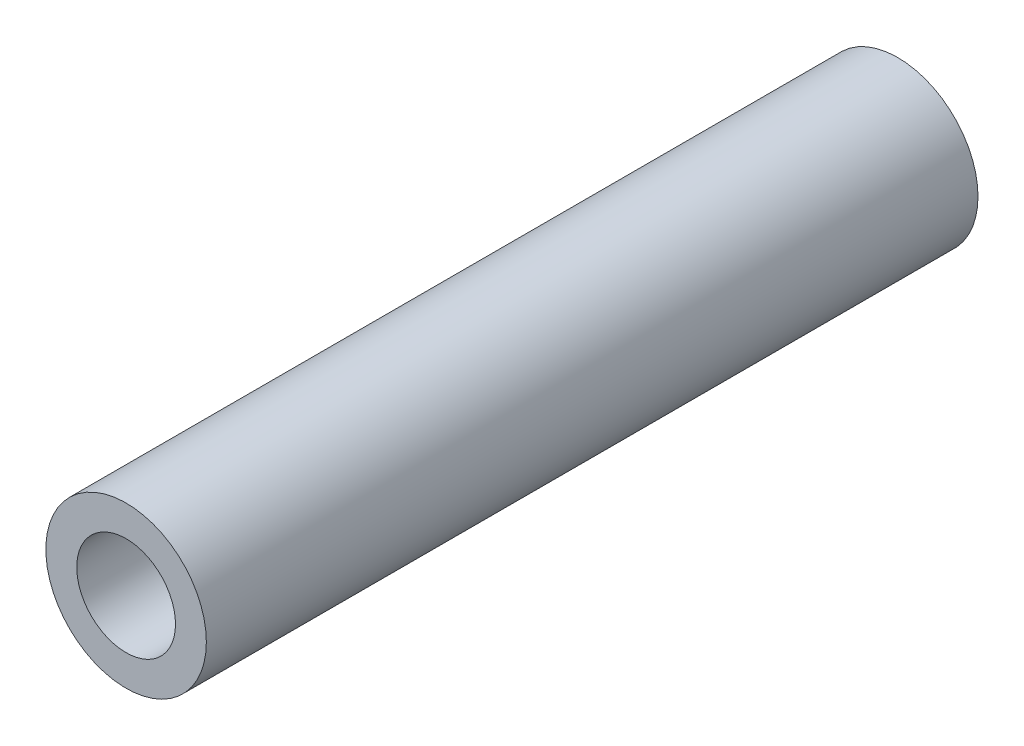
SolidWorks part; units mm, degrees
ref_plane "Спереди" through (0, 0, 0) normal (0, 0, 1) x (1, 0, 0)
ref_plane "Сверху" through (0, 0, 0) normal (0, 1, 0) x (1, 0, 0)
ref_plane "Справа" through (0, 0, 0) normal (1, 0, 0) x (0, 0, -1)
sketch "Эскиз1" plane through (0, 0, 0) normal (0, 0, 1) x (1, 0, 0)
  circle A0 centre (0, 0) radius 4
  circle A1 centre (0, 0) radius 6.5
extrude "Бобышка-Вытянуть1" add sketch "Эскиз1" along normal up to surface (62.5 mm away)
